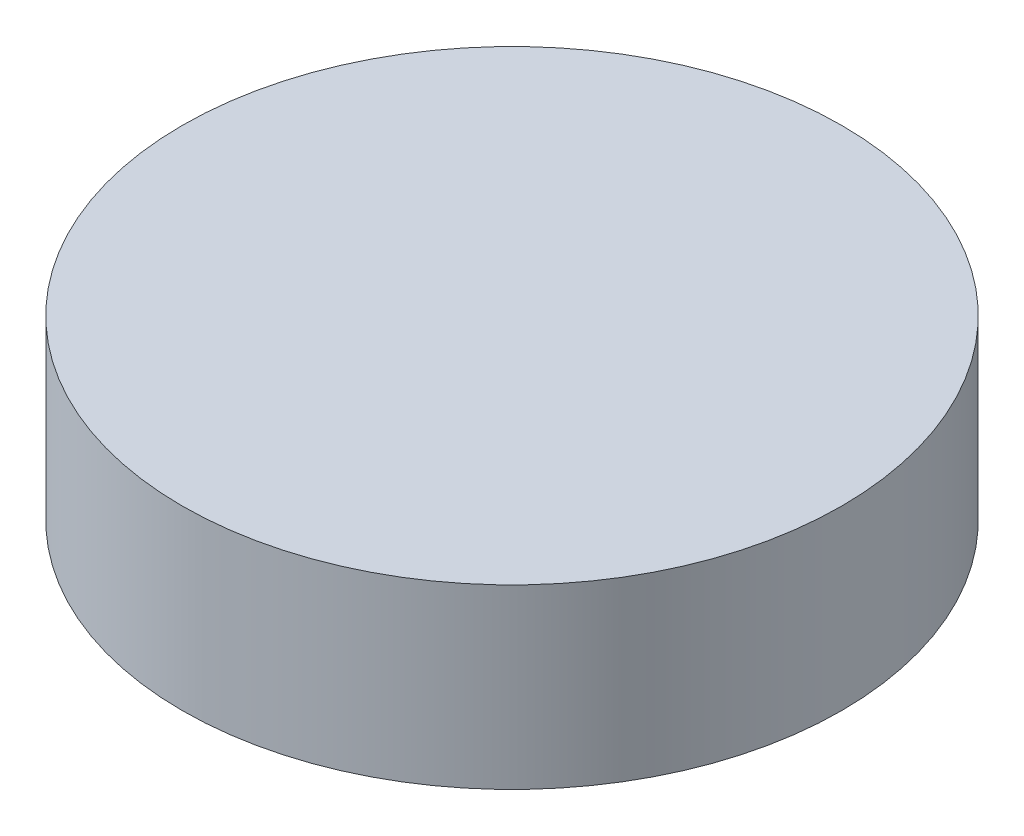
SolidWorks part; units mm, degrees
ref_plane "Front Plane" through (0, 0, 0) normal (0, 0, 1) x (1, 0, 0)
ref_plane "Top Plane" through (0, 0, 0) normal (0, 1, 0) x (1, 0, 0)
ref_plane "Right Plane" through (0, 0, 0) normal (1, 0, 0) x (0, 0, -1)
sketch "Sketch1" plane through (0, 0, 0) normal (0, 1, 0) x (1, 0, 0)
  circle A0 centre (0, 0) radius 20.5
  circle A1 centre (0, 0) radius 23.5
  circle A2 centre (0, 0) radius 25
  circle A3 centre (0, 0) radius 21.4
  circle A4 centre (0, 0) radius 25.5
  circle A5 centre (8.6, 0) radius 1.55
  circle A6 centre (-8.6, 0) radius 1.55
  point P11 (0, 0)
  dimension "D1" = 41
  dimension "D3" = 50
  dimension "D4" = 51
  dimension "D5" = 42.8
  dimension "D6" = 3.1
  dimension "D2" = 3
  dimension "D7" = 8.6
  dimension "D8" = 8.6
extrude "Boss-Extrude1" add sketch "Sketch1" along normal blind 11.5 contours A0 A6 A5 | A3 A0 region at (0, 0, 0) region at (-20.7947, 0, 0)
extrude "Boss-Extrude2" add sketch "Sketch1<3>" along normal blind 11.5 and the other way blind 5 contours A6 | A5 region at (8.6, 0, 0) region at (-8.6, 0, 0)
sketch "Sketch1<3>" plane through (0, 0, 0) normal (0, 1, 0) x (1, 0, 0) same geometry as "Sketch1"
equation "\"D5@Sketch1\"=\"D4@Sketch1\"-8.2"
equation "\"D8@Sketch1\"=\"D7@Sketch1\""
